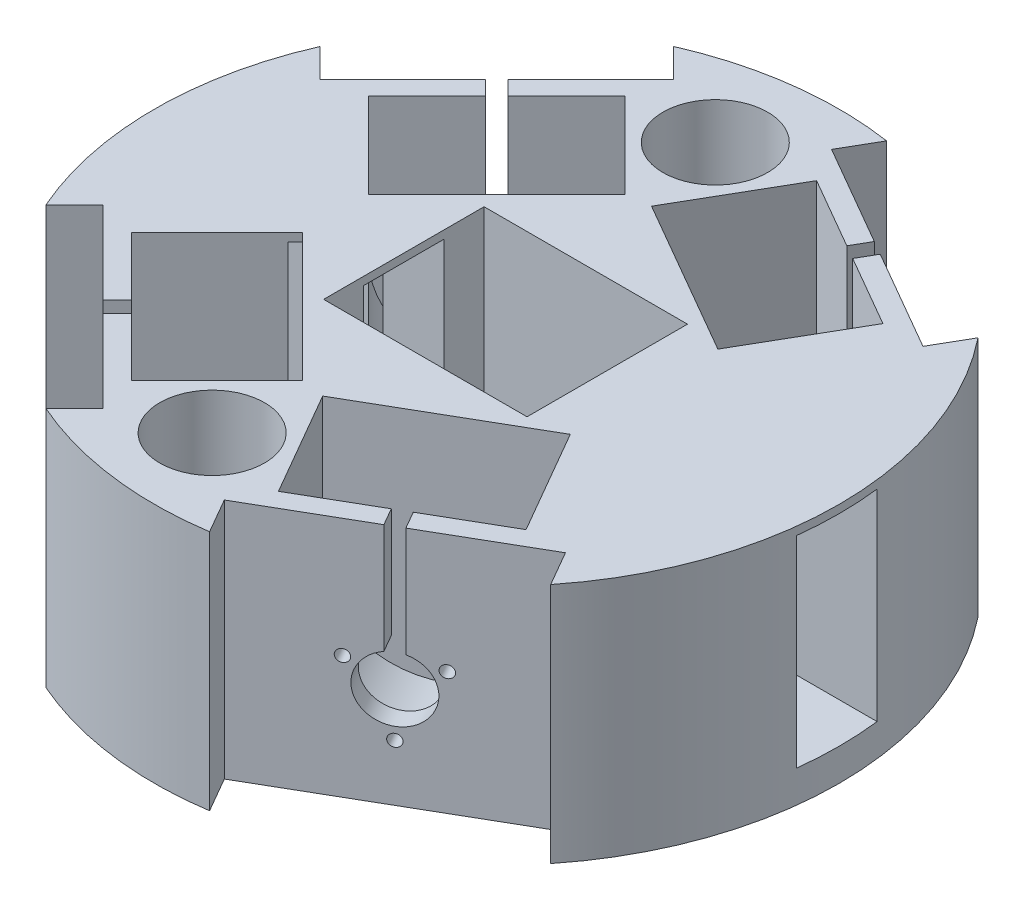
SolidWorks part; units mm, degrees
note: The reader was unsure of these and kept them because the rebuilt part matched: shared geometry of "Esboço3<10>".
ref_plane "Plano frontal" through (0, 0, 0) normal (0, 0, 1) x (1, 0, 0)
ref_plane "Plano superior" through (0, 0, 0) normal (0, 1, 0) x (1, 0, 0)
ref_plane "Plano direito" through (0, 0, 0) normal (1, 0, 0) x (0, 0, -1)
sketch "Esboço1" plane through (0, 0, 0) normal (0, 1, 0) x (1, 0, 0)
  line L0 (0, -20.0389) -> (0, 0) construction
  line L1 (0, 0) -> (-50000, 0) construction
  line L2 (0, 0) -> (-35355.3391, -35355.3391) construction
  line L3 (-77.8846, -34.044) -> (-34.044, -77.8846) construction
  line L4 (12.7259, -84.042) -> (66.4195, -53.042) construction
  line L5 (0, 0) -> (25000, -43301.2702) construction
  line L6 (12.7259, 84.042) -> (66.4195, 53.042) construction
  line L7 (-77.8846, 34.044) -> (-34.044, 77.8846) construction
  line L10 (-70.8135, -26.9729) -> (-26.9729, -70.8135)
  line L15 (-70.8135, -26.9729) -> (-77.8846, -34.044)
  line L16 (-26.9729, -70.8135) -> (-34.044, -77.8846)
  line L17 (7.7259, -75.3817) -> (61.4195, -44.3817)
  line L18 (66.4195, -53.042) -> (61.4195, -44.3817)
  line L19 (12.7259, -84.042) -> (7.7259, -75.3817)
  line L20 (66.4195, 53.042) -> (61.4195, 44.3817)
  line L21 (7.7259, 75.3817) -> (61.4195, 44.3817)
  line L22 (12.7259, 84.042) -> (7.7259, 75.3817)
  line L23 (-26.9729, 70.8135) -> (-34.044, 77.8846)
  line L24 (-70.8135, 26.9729) -> (-26.9729, 70.8135)
  line L25 (-70.8135, 26.9729) -> (-77.8846, 34.044)
  arc A0 (-34.044, -77.8846) -> (12.7259, -84.042) centre (0, 0) ccw
  arc A1 (66.4195, -53.042) -> (66.4195, 53.042) centre (0, 0) ccw
  arc A2 (-77.8846, 34.044) -> (-77.8846, -34.044) centre (0, 0) ccw
  arc A3 (12.7259, 84.042) -> (-34.044, 77.8846) centre (0, 0) ccw
  point P6 (0, 0)
  point P13 (-55.9643, -55.9643)
  point P17 (39.5727, -68.542)
  point P48 (-48.8932, -48.8932)
  point P51 (34.5727, -59.8817)
  point P52 (-74.3491, -30.5084)
  point P57 (-74.3491, 30.5084)
  dimension "D1" = 170
  dimension "D2" = 45
  dimension "D3" = 62
  dimension "D4" = 30
extrude "Base" add sketch "Esboço1" along normal blind 60
sketch "Esboço3" plane through (-48.8932, 0, 48.8932) normal (-0.7071, 0, 0.7071) x (0.7071, 0, 0.7071)
  line L0 (0, 0) -> (0, 60) construction
  line L1 (-31, 0) -> (31, 0) construction
  line L2 (-31, 60) -> (31, 60) construction
  line L3 (-2, 25) -> (2, 25)
  line L4 (-22.5, 25) -> (22.5, 25)
  line L5 (-22.5, 25) -> (-22.5, 80)
  line L6 (-22.5, 80) -> (22.5, 80)
  line L7 (22.5, 25) -> (22.5, 80)
  line L8 (-22.5, 25) -> (22.5, 80) construction
  line L9 (-22.5, 80) -> (22.5, 25) construction
  line L10 (-2, 25) -> (-2, 70)
  line L11 (2, 25) -> (2, 70)
  line L12 (-2, 70) -> (2, 70)
  arc A0 (-22.5, 25) -> (22.5, 25) centre (0, 25) ccw
  circle A1 centre (0, 25) radius 2
  circle A2 centre (0, 14) radius 1.5
  circle A3 centre (-9.5263, 30.5) radius 1.5
  circle A4 centre (9.5263, 30.5) radius 1.5
  circle A5 centre (0, 25) radius 8
  point P12 (0, 52.5)
  point P22 (0, 25)
  line M3 (31, 60) -> (-31, 60)
  dimension "D1" = 45
  dimension "D4" = 11
  dimension "D5" = 3
  dimension "D8" = 16
  dimension "D2" = 25
  dimension "D3" = 55
  dimension "D7" = 45
  dimension "D6" = 3
  dimension "4mm eixomotor" = 4
extrude "Motor-traseiro" cut sketch "Esboço3" against normal blind 30 from offset 5 contours L4 A1 | L4 A1 | L12 L10 L11 M3 | A1 L11 L10 M3 | A1 L4 A0 A2 | L4 A5 A1 offset against normal yes
extrude "Motor-eixo" cut sketch "Esboço3<10>" against normal blind 25 contours L4 A1 | L4 A1 | L4 A5 A1 | L4 A5 L11 | L10 A5 L4 | A4 | A2 | A3
sketch "Esboço3<10>" plane through (-48.8932, 0, 48.8932) normal (-0.7071, 0, 0.7071) x (0.7071, 0, 0.7071) same geometry as "Esboço3"
pattern_circular "PadrãoCircular1" count 2 every 285 about axis through (0, 60, 0) along (0, -1, 0) of "Motor-traseiro", "Motor-eixo"
mirror "Espelhar3" about plane through (0, 0, 0) normal (0, 0, 1) of "PadrãoCircular1", "Motor-eixo", "Motor-traseiro"
sketch "Esboço16" plane through (0, 60, 0) normal (0, 1, 0) x (1, 0, 0)
  line L0 (116.6673, 0) -> (-116.6673, 0) construction
  line L1 (-130.5262, -991.4449) -> (6395.7834, 48580.7982) construction
  circle A0 centre (-8.2232, -62.461) radius 13
  circle A1 centre (-8.2232, 62.461) radius 13
  point P4 (0, 0)
  point P8 (0, 0)
  dimension "D3" = 26
  dimension "D1" = 97.5
  dimension "D2" = 63
extrude "Capacitores" cut sketch "Esboço16" against normal blind 45
sketch "Esboço18" plane through (0, 0, 0) normal (0, -1, 0) x (1, 0, 0)
  line L0 (-105.6725, 0) -> (112.2038, 0) construction
  line L1 (-33, -10) -> (-33, 10)
  line L2 (-33, 10) -> (-8, 35)
  line L3 (-8, 35) -> (0, 35)
  line L4 (0, 35) -> (40, 13)
  line L5 (40, 13) -> (40, -13)
  line L6 (0, -35) -> (40, -13)
  line L7 (-8, -35) -> (0, -35)
  line L8 (-33, -10) -> (-8, -35)
  point P5 (0, 0)
  point P11 (3.0054, 32.0146)
  point P12 (40, 0)
  point P15 (-33, 0)
  dimension "D1" = 10
  dimension "D2" = 35
  dimension "D3" = 13
  dimension "D4" = 25
  dimension "D5" = 40
  dimension "D6" = 33
extrude "Corte-extrusão1" cut sketch "Esboço18" against normal blind 8
sketch "Esboço19" plane through (0, 8, 0) normal (0, -1, 0) x (1, 0, 0)
  line L0 (-8, 35) -> (-33, 10) construction
  line L1 (-23.0806, 19.9194) -> (27.4194, 19.9194)
  line L2 (-23.0806, 19.9194) -> (-23.0806, -19.9194)
  line L3 (-23.0806, -19.9194) -> (27.4194, -19.9194)
  line L4 (27.4194, 19.9194) -> (27.4194, -19.9194)
  line L5 (0, -35) -> (40, -13) construction
  line L6 (-33, -10) -> (-8, -35) construction
  point P8 (0, 0)
  point P9 (0, 0)
  dimension "D1" = 50.5
extrude "Corte-extrusão2" cut sketch "Esboço19" against normal through all
sketch "Esboço21" plane through (-23.0806, 0, 0) normal (1, 0, 0) x (0, 0, -1)
  line L0 (0, 8) -> (0, 23.4218) construction
  line L2 (-19.9194, 8) -> (19.9194, 8) construction
  line L3 (-10, 8) -> (10, 8)
  line L4 (-10, 8) -> (-10, 58)
  line L5 (-10, 58) -> (10, 58)
  line L6 (10, 8) -> (10, 58)
  line L7 (-10, 8) -> (10, 58) construction
  line L8 (-10, 58) -> (10, 8) construction
  point P1 (0, 33)
  point P8 (0, 0)
  dimension "D1" = 50
  dimension "D2" = 20
extrude "Corte-extrusão3" cut sketch "Esboço21" against normal through all both and the other way through all
sketch "Esboço24" plane through (-33, 0, 0) normal (1, 0, 0) x (0, 0, -1)
  line L0 (0, 0) -> (0, 13.6383) construction
  line L2 (-10, 0) -> (10, 0) construction
  line L3 (-10, 8) -> (10, 8) construction
  line L4 (-10, 3) -> (10, 3)
  line L5 (-10, 3) -> (-10, 8)
  line L6 (-10, 8) -> (10, 8)
  line L7 (10, 3) -> (10, 8)
  line L8 (-10, 3) -> (10, 8) construction
  line L9 (-10, 8) -> (10, 3) construction
  point P1 (0, 6.8192)
  point P5 (0, 0)
  point P6 (0, 5.5)
  point P13 (-10, 8)
  dimension "D1" = 5
extrude "Corte-extrusão6" cut sketch "Esboço24" against normal through all
sketch "Esboço25" plane through (0, 8, 0) normal (0, -1, 0) x (1, 0, 0)
  line L0 (-15.3826, 0) -> (-7.6853, 0) construction
  line L1 (-23.0806, 19.9194) -> (-23.0806, 10) construction
  line L3 (27.4194, 19.9194) -> (-23.0806, 19.9194) construction
  line L4 (27.4194, 10) -> (27.4194, 19.9194) construction
  circle A0 centre (-26.0806, 13) radius 1.5
  circle A1 centre (-10.0806, 25.9194) radius 1.5
  circle A2 centre (5.4194, 25.9194) radius 1.5
  circle A3 centre (30.4194, 13) radius 1.5
  circle A4 centre (30.4194, -13) radius 1.5
  circle A5 centre (5.4194, -25.9194) radius 1.5
  circle A6 centre (-10.0806, -25.9194) radius 1.5
  circle A7 centre (-26.0806, -13) radius 1.5
  dimension "D1" = 3
  dimension "D2" = 6.9194
  dimension "D3" = 3
  dimension "D4" = 3
  dimension "D5" = 6.9194
  dimension "D6" = 3
  dimension "D7" = 6
  dimension "D8" = 6
  dimension "D9" = 3
  dimension "D10" = 3
  dimension "D11" = 22
  dimension "D12" = 13
extrude "Corte-extrusão7" cut sketch "Esboço25" against normal blind 10
